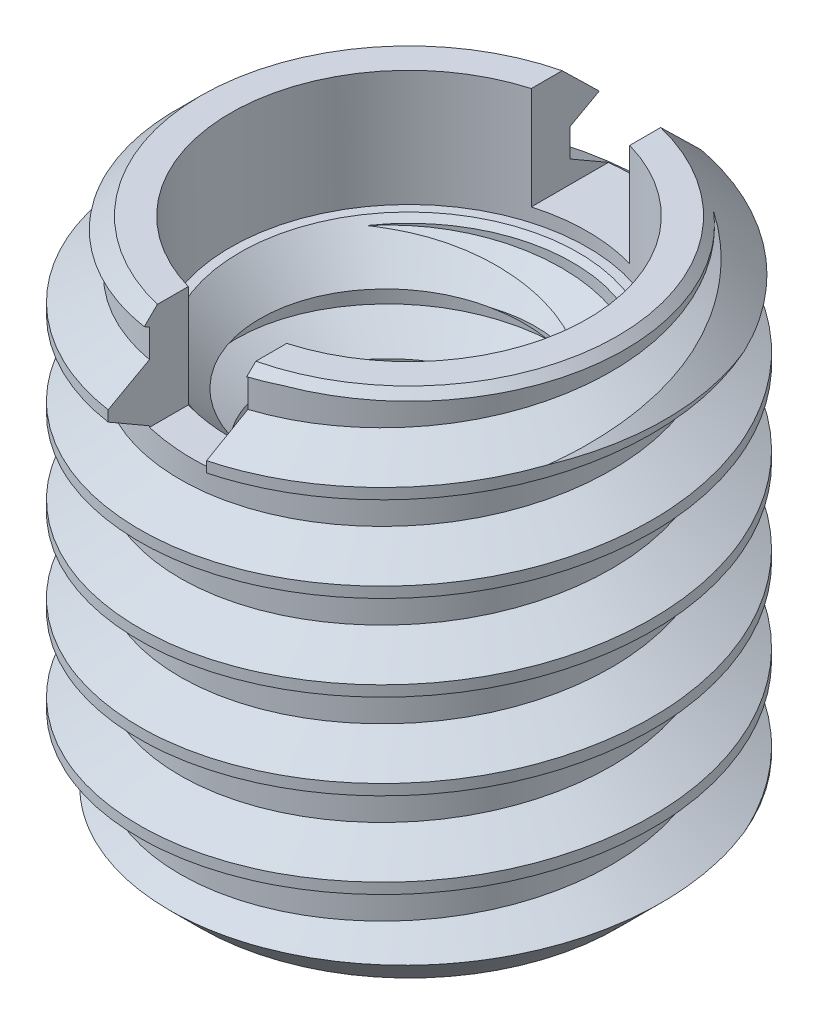
SolidWorks part; units mm, degrees
material "Plain Carbon Steel"
ref_plane "Front Plane" through (0, 0, 0) normal (0, 0, 1) x (1, 0, 0)
ref_plane "Top Plane" through (0, 0, 0) normal (0, 1, 0) x (1, 0, 0)
ref_plane "Right Plane" through (0, 0, 0) normal (1, 0, 0) x (0, 0, -1)
sketch "Sketch1" plane through (0, 0, 0) normal (0, 1, 0) x (1, 0, 0)
  line L0 (-4.7625, 0) -> (4.7625, 0) construction
  circle A0 centre (0, 0) radius 4.7625
  dimension "External Thread OD" = 9.525
extrude "Extrude1" add sketch "Sketch1" against normal blind 9.525
sketch "Sketch4" plane through (0, 0, 0) normal (0, 1, 0) x (1, 0, 0)
  circle A2 centre (0, 0) radius 3.175
  point P0 (-3.175, 0)
  dimension "Internal Thread OD" = 6.35
sketch "Sketch2" plane through (0, 0, 0) normal (0, 1, 0) x (1, 0, 0)
  circle A0 centre (0, 0) radius 3.3147
  dimension "A" = 6.6294
extrude "Extrude2" cut sketch "Sketch2" against normal blind 2.159
sketch "Sketch3" plane through (0, 0, 0) normal (0, 0, 1) x (1, 0, 0)
  line L5 (-0.9144, 0) -> (0.9144, 0)
  line L6 (-0.9144, 0) -> (-0.9144, -1.905)
  line L7 (-0.9144, -1.905) -> (0.9144, -1.905)
  line L8 (0.9144, 0) -> (0.9144, -1.905)
  dimension "B" = 1.8288
  dimension "C" = 1.905
extrude "Extrude3" cut sketch "Sketch3" along normal through all and the other way through all
curve "Helix/Spiral1" pitch 1.27 height 10.795 turns 8.5 parameters "Internal Thread Height"=10.795, "Internal Thread Pitch"=1.27
sketch "Sketch5" plane through (0, 0, 0) normal (0, 0, 1) x (1, 0, 0)
  line L0 (-2.2126, 1.1906) -> (-2.2126, -0.0794) construction
  line L1 (-2.2126, -0.0794) -> (-3.3125, 0.5556) construction
  line L2 (-3.3125, 0.5556) -> (-2.2126, 1.1906) construction
  line L3 (-2.2126, 0.5556) -> (-2.3501, 0.5556) construction
  line L4 (-2.3501, 0.5556) -> (-3.0375, 0.5556) construction
  line L5 (-3.175, 0.5556) -> (-3.3125, 0.5556) construction
  line L6 (-3.175, 0.635) -> (-3.175, 0.4763) construction
  line L7 (-2.3501, 0) -> (-2.3501, 1.1113) construction
  line L8 (-3.175, 0.4763) -> (-3.175, 0) construction
  line L9 (-3.175, 0) -> (-2.3501, 0) construction
  line L10 (-3.0375, 0.7144) -> (-3.0375, 0.3969)
  line L11 (-3.0375, 0.3969) -> (-2.2814, -0.0397)
  line L12 (-2.2814, -0.0397) -> (-2.2814, 1.1509)
  line L13 (-2.2814, 1.1509) -> (-3.0375, 0.7144)
  line L14 (-3.175, 0.5556) -> (-3.0375, 0.5556) construction
  point P18 (-2.2814, 0.5556)
  dimension "D1" = 1.27
  dimension "D2" = 0.1588
sketch "Sketch6" plane through (0, 0, 0) normal (0, 1, 0) x (-1, 0, 0)
  circle A0 centre (0, 0) radius 2.3501
extrude "Extrude4" cut sketch "Sketch6" against normal through all
chamfer "Chamfer1" distance 0.7937 angle 45 2 edges at (0, -9.525, 2.3501) (0, -2.159, 2.3501)
sweep "Cut-Sweep1" cut profiles "Sketch5" path "Helix/Spiral1"
sketch "Sketch7" plane through (0, 0, 0) normal (0, 1, 0) x (1, 0, 0)
  circle A0 centre (0, 0) radius 4.7625 construction
  circle A1 centre (0, 0) radius 4.7625
  point P3 (-4.7625, 0)
curve "Helix/Spiral2" pitch 1.5875 height 10.795 turns 6.8 parameters "External Thread Height"=10.795, "External Thread Pitch"=1.5875
sketch "Sketch8" plane through (0, 0, 0) normal (0, 0, 1) x (1, 0, 0)
  line L0 (-4.9344, 1.4883) -> (-4.9344, -0.0992) construction
  line L1 (-4.9344, 1.4883) -> (-3.5595, 0.6945) construction
  line L2 (-3.5595, 0.6945) -> (-4.9344, -0.0992) construction
  line L3 (-4.7625, 1.3891) -> (-4.7625, 0) construction
  line L4 (-3.7314, 0.7937) -> (-3.7314, 0.5953) construction
  line L5 (-4.8484, 1.4387) -> (-4.0132, 0.9565)
  line L6 (-4.8484, 1.4387) -> (-4.8484, -0.0496)
  line L7 (-4.8484, -0.0496) -> (-4.0132, 0.4326)
  line L8 (-4.9344, 0.6945) -> (-4.7625, 0.6945) construction
  line L9 (-3.7314, 0.6945) -> (-3.5595, 0.6945) construction
  line L10 (-4.0132, 0.9565) -> (-4.0132, 0.4326)
  line L11 (-4.0132, 0.6945) -> (-3.7314, 0.6945) construction
  line L12 (0, 0) -> (0, 1.4883) construction
  point P13 (-4.8484, 0.6945)
  dimension "D1" = 1.5875
  dimension "D2" = 0.1984
chamfer "Chamfer2" distance 0.893 angle 45 3 edges at (0, -9.525, 4.7625) (4.7625, 0, 0) (-4.7625, 0, 0)
sweep "Cut-Sweep2" cut profiles "Sketch8" path "Helix/Spiral2"
equation "\"Internal Thread Height@Helix/Spiral1\" = \"Internal Thread Pitch@Helix/Spiral1\" + \"Length@Extrude1\""
equation "\"D1@Sketch5\" = \"Internal Thread Pitch@Helix/Spiral1\""
equation "\"D2@Sketch5\" = \"D1@Sketch5\" / 8"
equation "\"D1@Chamfer1\" = \"Internal Thread Pitch@Helix/Spiral1\" * 5 / 8"
equation "\"External Thread Height@Helix/Spiral2\" = \"Internal Thread Height@Helix/Spiral1\""
equation "\"D1@Sketch8\" = \"External Thread Pitch@Helix/Spiral2\""
equation "\"D2@Sketch8\" = \"D1@Sketch8\" / 8"
equation "\"D1@Chamfer2\" = \"External Thread Pitch@Helix/Spiral2\" * 4.5 / 8"
